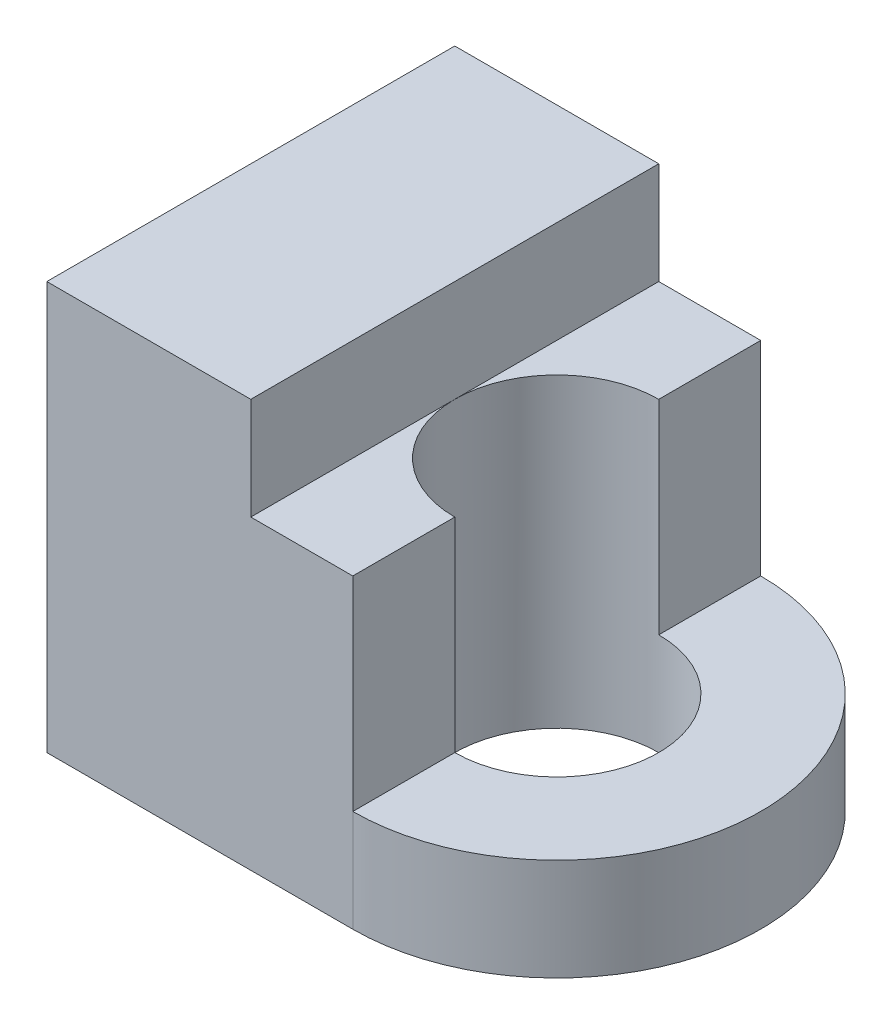
SolidWorks part; units mm, degrees
ref_plane "前基準面" through (0, 0, 0) normal (0, 0, 1) x (1, 0, 0)
ref_plane "上基準面" through (0, 0, 0) normal (0, 1, 0) x (1, 0, 0)
ref_plane "右基準面" through (0, 0, 0) normal (1, 0, 0) x (0, 0, -1)
sketch "草圖1" plane through (0, 0, 0) normal (0, 1, 0) x (1, 0, 0)
  line L0 (-5, -10) -> (-5, 10)
  line L1 (0, -10) -> (-15, -10)
  line L3 (0, 10) -> (-15, 10)
  line L4 (-15, -10) -> (-15, 10)
  line L5 (0, 5) -> (0, 10)
  line L6 (0, -5) -> (0, -10)
  circle A0 centre (0, 0) radius 5
  arc A1 (0, -10) -> (0, 10) centre (0, 0) ccw
  point P11 (-5, 0)
  dimension "D1" = 20
  dimension "D2" = 10
  dimension "D3" = 15
extrude "填料-伸長2" add sketch "草圖1" along normal blind 5 contours A0 | A1 L3 L4 L1 region at (0, 0, 0)
extrude "填料-伸長4" add sketch "草圖1<4>" along normal blind 15 contours A0 L0 L1 L6 | A0 L5 L3 L0 | L4 L1 L0 L3 region at (-10, 0, 0) region at (-2.7444, 0, 6.861) region at (-2.7444, 0, -6.861)
sketch "草圖1<4>" plane through (0, 0, 0) normal (0, 1, 0) x (1, 0, 0) same geometry as "草圖1"
extrude "填料-伸長5" add sketch "草圖1<5>" along normal blind 20 contours L4 L1 L0 L3 region at (-10, 0, 0)
sketch "草圖1<5>" plane through (0, 0, 0) normal (0, 1, 0) x (1, 0, 0) same geometry as "草圖1"
